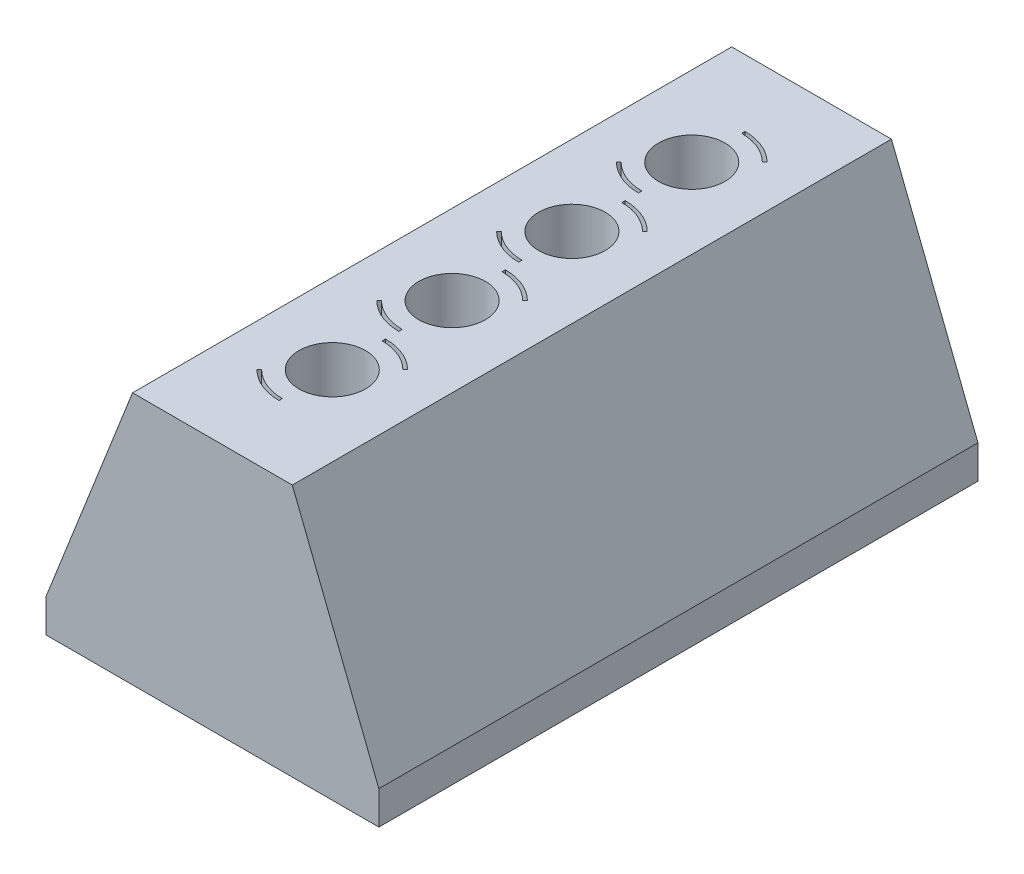
SolidWorks part; units mm, degrees
material "3.3549 (EN-AW 5182)"
ref_plane "Piano frontale" through (0, 0, 0) normal (0, 0, 1) x (1, 0, 0)
ref_plane "Piano superiore" through (0, 0, 0) normal (0, 1, 0) x (1, 0, 0)
ref_plane "Piano destro" through (0, 0, 0) normal (1, 0, 0) x (0, 0, -1)
sketch "Schizzo1" plane through (0, 0, 0) normal (0, 0, 1) x (1, 0, 0)
  line L0 (-125, 0) -> (125, 0)
  line L2 (60, 190) -> (-60, 190)
  line L4 (-125, 0) -> (-125, 25)
  line L5 (-125, 25) -> (-60, 190)
  line L6 (125, 0) -> (125, 25)
  line L7 (125, 25) -> (60, 190)
  point P2 (0, 190)
  dimension "D1" = 190
  dimension "D2" = 120
  dimension "D3" = 250
  dimension "D4" = 25
extrude "Estrusione-Estrusione1" add sketch "Schizzo1" along normal mid plane 450
sketch "Schizzo2" plane through (0, 190, 0) normal (0, 1, 0) x (1, 0, 0)
  line L0 (0, -225) -> (0, -135)
  line L1 (60, -225) -> (-60, -225) construction
  line L2 (0, -135) -> (0, -45)
  line L3 (0, -45) -> (0, 45)
  line L4 (0, 45) -> (0, 135)
  line L5 (0, 135) -> (0, 225)
  line L6 (60, 225) -> (-60, 225) construction
  circle A0 centre (0, -135) radius 25
  circle A1 centre (0, -45) radius 25
  circle A2 centre (0, 45) radius 25
  circle A3 centre (0, 135) radius 25
  dimension "D1" = 50
extrude "Taglio-Estrusione1" cut sketch "Schizzo2" against normal blind 90 contours L0 A0 L2 | L2 A0 L0 | L2 A1 L3 | L3 A1 L2 | L3 A2 L4 | L4 A2 L3 | L4 A3 L5 | L5 A3 L4 region at (-10.6103, 190, 135) region at (-10.6103, 190, -135) region at (10.6103, 190, -135) region at (-10.6103, 190, -45) region at (10.6103, 190, -45) region at (-10.6103, 190, 45) region at (10.6103, 190, 45) region at (10.6103, 190, 135)
shell "Svuota1" thickness 15 removed face at (0, 71.6667, 225)
sketch "Schizzo4" plane through (0, 85, 0) normal (0, -1, 0) x (1, 0, 0)
  circle A0 centre (0, -135) radius 40 construction
  circle A1 centre (0, -45) radius 40 construction
  circle A2 centre (0, 45) radius 40 construction
  circle A3 centre (0, 135) radius 40 construction
  circle A4 centre (0, -135) radius 40
  circle A5 centre (0, -45) radius 40
  circle A6 centre (0, 45) radius 40
  circle A7 centre (0, 135) radius 40
  circle M1 centre (0, 135) radius 40
extrude "Taglio-Estrusione2" cut sketch "Schizzo4" against normal blind 20 contours M1 | A6 | A5 | A4 region at (0, 85, -135) region at (0, 85, -45) region at (0, 85, 45) region at (0, 85, 135)
ref_plane "Piano1" through (0, 105, 0) normal (0, 1, 0) x (1, 0, 0)
sketch "Schizzo6" plane through (0, 105, 0) normal (0, 1, 0) x (1, 0, 0)
  line L0 (-77.3629, 210) -> (-77.3629, -225)
  line L1 (-77.3629, 210) -> (-77.3629, -225)
  line L2 (77.3629, -225) -> (77.3629, 210)
  line L3 (77.3629, -225) -> (77.3629, 210)
  line L4 (-77.3629, -225) -> (77.3629, -225)
  line L5 (-77.3629, 210) -> (77.3629, 210)
  circle A0 centre (0, 135) radius 40 construction
  circle A1 centre (0, 45) radius 40 construction
  circle A2 centre (0, -45) radius 40 construction
  circle A3 centre (0, -135) radius 40 construction
  circle A4 centre (0, 135) radius 40
  circle A5 centre (0, 45) radius 40
  circle A6 centre (0, -45) radius 40
  circle A7 centre (0, -135) radius 40
extrude "Estrusione-Estrusione2" add sketch "Schizzo6" along normal blind 10
sketch "Schizzo7" plane through (0, 0, 225) normal (0, 0, 1) x (1, 0, 0)
  line L6 (-125, 25) -> (-125, 0)
  line L7 (-125, 0) -> (125, 0)
  line L8 (125, 0) -> (125, 25)
  line L9 (125, 25) -> (60, 190)
  line L10 (60, 190) -> (-60, 190)
  line L11 (-60, 190) -> (-125, 25)
  line L12 (-125, 25) -> (-125, 0)
  line L13 (-125, 0) -> (125, 0)
  line L14 (125, 0) -> (125, 25)
  line L15 (125, 25) -> (60, 190)
  line L16 (60, 190) -> (-60, 190)
  line L17 (-60, 190) -> (-125, 25)
  dimension "D1" = 0
extrude "Estrusione-Estrusione3" add sketch "Schizzo7" against normal blind 15
sketch "Schizzo12" plane through (0, 0, -210) normal (0, 0, 1) x (1, 0, 0)
  line L0 (0, 105) -> (0, 15)
  line L1 (77.3629, 105) -> (-77.3629, 105) construction
  line L2 (-110, 15) -> (110, 15) construction
  circle A0 centre (0, 60) radius 35
  dimension "D1" = 70
extrude "Taglio-Estrusione12" cut sketch "Schizzo12" against normal through all contours L0 A0 | L0 A0 region at (14.8545, 60, -210) region at (-14.8545, 60, -210)
sketch "Schizzo13" plane through (0, 190, 0) normal (0, 1, 0) x (1, 0, 0)
  line L0 (0, 97.5) -> (0, 95)
  line L1 (-26.5165, 108.4835) -> (-28.2843, 106.7157)
  line L2 (26.5165, 161.5165) -> (28.2843, 163.2843)
  line L3 (0, 172.5) -> (0, 175)
  line L4 (-26.5165, 18.4835) -> (-28.2843, 16.7157)
  line L5 (0, 7.5) -> (0, 5)
  line L6 (26.5165, 71.5165) -> (28.2843, 73.2843)
  line L7 (0, 82.5) -> (0, 85)
  line L8 (-26.5165, -71.5165) -> (-28.2843, -73.2843)
  line L9 (0, -82.5) -> (0, -85)
  line L10 (26.5165, -18.4835) -> (28.2843, -16.7157)
  line L11 (0, -7.5) -> (0, -5)
  line L12 (-26.5165, -161.5165) -> (-28.2843, -163.2843)
  line L13 (0, -172.5) -> (0, -175)
  line L14 (26.5165, -108.4835) -> (28.2843, -106.7157)
  line L15 (0, -97.5) -> (0, -95)
  arc A0 (-26.5165, 108.4835) -> (0, 97.5) centre (0, 135) ccw
  arc A1 (-28.2843, 106.7157) -> (0, 95) centre (0, 135) ccw
  arc A2 (26.5165, 161.5165) -> (0, 172.5) centre (0, 135) ccw
  arc A3 (28.2843, 163.2843) -> (0, 175) centre (0, 135) ccw
  arc A4 (-26.5165, 18.4835) -> (0, 7.5) centre (0, 45) ccw
  arc A5 (-28.2843, 16.7157) -> (0, 5) centre (0, 45) ccw
  arc A6 (26.5165, 71.5165) -> (0, 82.5) centre (0, 45) ccw
  arc A7 (28.2843, 73.2843) -> (0, 85) centre (0, 45) ccw
  arc A8 (-26.5165, -71.5165) -> (0, -82.5) centre (0, -45) ccw
  arc A9 (-28.2843, -73.2843) -> (0, -85) centre (0, -45) ccw
  arc A10 (26.5165, -18.4835) -> (0, -7.5) centre (0, -45) ccw
  arc A11 (28.2843, -16.7157) -> (0, -5) centre (0, -45) ccw
  arc A12 (-26.5165, -161.5165) -> (0, -172.5) centre (0, -135) ccw
  arc A13 (-28.2843, -163.2843) -> (0, -175) centre (0, -135) ccw
  arc A14 (26.5165, -108.4835) -> (0, -97.5) centre (0, -135) ccw
  arc A15 (28.2843, -106.7157) -> (0, -95) centre (0, -135) ccw
  dimension "D1" = 75
  dimension "D2" = 80
  dimension "D3" = 45
  dimension "D5" = 4
  dimension "D4" = 2
extrude "Taglio-Estrusione13" cut sketch "Schizzo13" against normal blind 20
